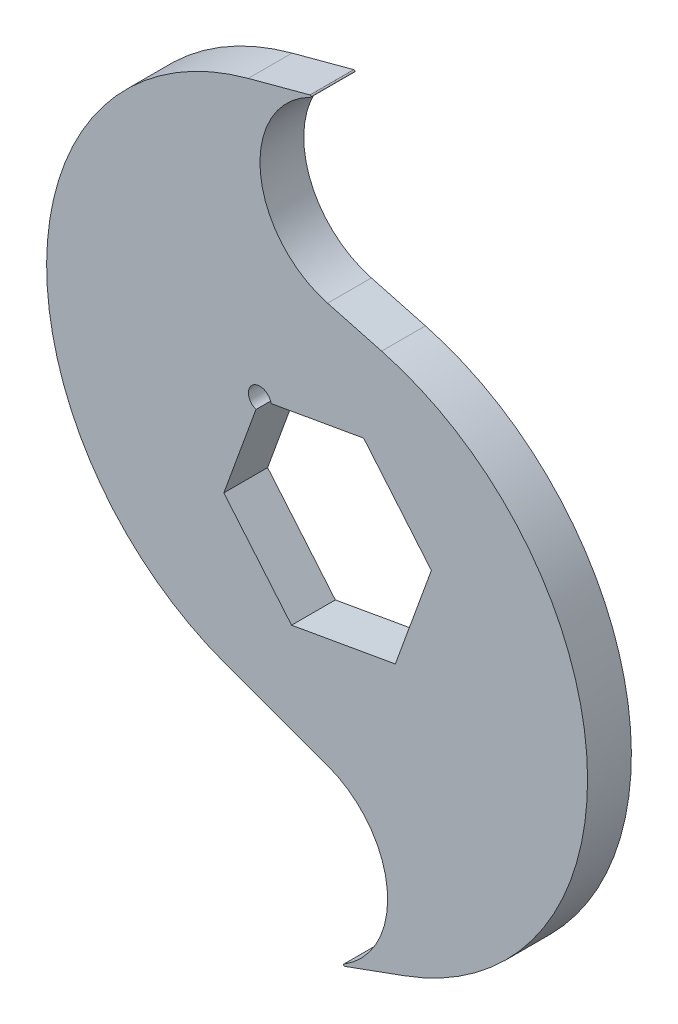
SolidWorks part; units mm, degrees
ref_plane "Front Plane" through (0, 0, 0) normal (0, 0, 1) x (1, 0, 0)
ref_plane "Top Plane" through (0, 0, 0) normal (0, 1, 0) x (1, 0, 0)
ref_plane "Right Plane" through (0, 0, 0) normal (1, 0, 0) x (0, 0, -1)
sketch "Sketch1" plane through (0, 0, 0) normal (0, 0, 1) x (1, 0, 0)
  line L0 (0, 52.07) -> (-11.0405, 49.1117)
  line L1 (0, 52.07) -> (0, 0) construction
  line L2 (0, -52.07) -> (10.7407, -48.1607)
  line L3 (0, 0) -> (0, -52.07) construction
  line L5 (-9.4263, 11.2338) -> (-14.4419, -2.5465)
  line L6 (-14.4419, -2.5465) -> (-5.0156, -13.7803)
  line L7 (-5.0156, -13.7803) -> (9.4263, -11.2338)
  line L8 (9.4263, -11.2338) -> (14.4419, 2.5465)
  line L9 (14.4419, 2.5465) -> (5.0156, 13.7803)
  line L10 (5.0156, 13.7803) -> (-9.4263, 11.2338)
  line L11 (0, 27.5355) -> (7.5237, 25.5195)
  line L12 (0, -28.2018) -> (-14.1906, -23.0368)
  circle A0 centre (0, 0) radius 52.07 construction
  arc A1 (0, 52.07) -> (0, 27.5355) centre (3.287, 39.8027) ccw
  arc A3 (0, -52.07) -> (0, -28.2018) centre (-4.3437, -40.1359) ccw
  arc A4 (10.7407, -48.1607) -> (7.5237, 25.5195) centre (-2.4834, -11.8278) ccw
  arc A5 (-11.0405, 49.1117) -> (-14.1906, -23.0368) centre (-1.2414, 12.5408) ccw
  circle A6 centre (0, 0) radius 12.7 construction
  circle A7 centre (-9.4263, 11.2338) radius 1.5875
  dimension "D4" = 70
  dimension "D5" = 25.4
  dimension "D1" = 104.14
  dimension "D6" = 12.7
  dimension "D8" = 3.175
  dimension "D2" = 11.43
  dimension "D3" = 75
  dimension "D7" = 40
extrude "Boss-Extrude1" add sketch "Sketch1" along normal mid plane 6.096 contours L0 A5 L12 A3 L2 A4 L11 A1 A7 L10 L9 L8 L7 L6 L5 region at (-10.698, 39.8027, 0)
fillet "Fillet1" radius 0.127 2 edges at (0, 52.07, 0) (0, -52.07, 0)
